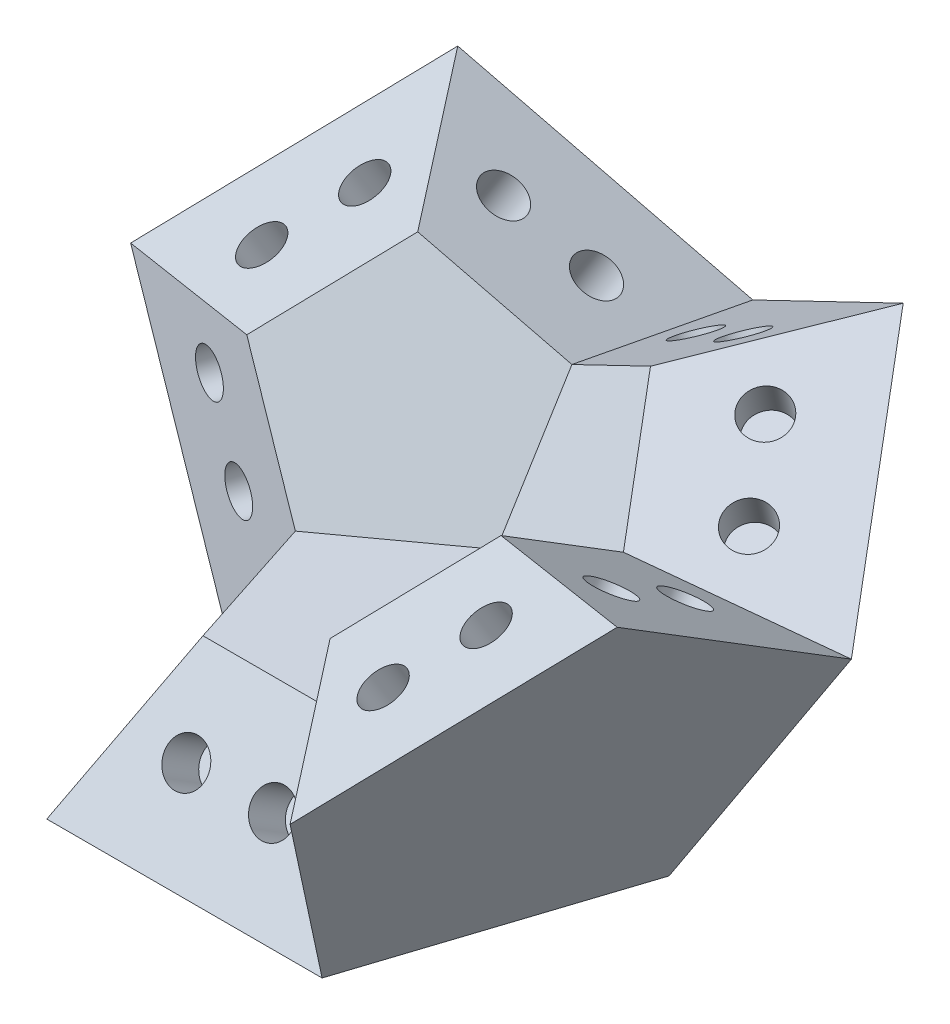
SolidWorks part; units mm, degrees
ref_plane "Front Plane" through (0, 0, 0) normal (0, 0, 1) x (1, 0, 0)
ref_plane "Top Plane" through (0, 0, 0) normal (0, 1, 0) x (1, 0, 0)
ref_plane "Right Plane" through (0, 0, 0) normal (1, 0, 0) x (0, 0, -1)
ref_axis "Axis1" through (0, 14.8487, 0) along (0, -1, 0)
sketch "Sketch1" plane through (0, 0, 0) normal (0, 1, 0) x (1, 0, 0)
  line L1 (0, 10.8033) -> (-10.2745, 3.3384)
  line L2 (-10.2745, 3.3384) -> (-6.35, -8.74)
  line L3 (-6.35, -8.74) -> (6.35, -8.74)
  line L4 (6.35, -8.74) -> (10.2745, 3.3384)
  line L5 (10.2745, 3.3384) -> (0, 10.8033)
  circle A0 centre (0, 0) radius 8.74 construction
  dimension "D1" = 12.7
extrude "Boss-Extrude1" add sketch "Sketch1" along normal blind 6.752 draft 31.717
mirror "Mirror1" [suppressed]
sketch "Sketch3" plane through (0, 3.9087, 6.3243) normal (0, 0.5257, 0.8507) x (1, 0, 0)
  line L0 (-2, -0.6262) -> (2, -0.6262) construction
  line L1 (-6.35, -4.5949) -> (6.35, -4.5949) construction
  line L2 (-2, -4.5949) -> (-2, 3.3426) construction
  circle A0 centre (-2, -0.6262) radius 1
  circle A1 centre (2, -0.6262) radius 1
  point P4 (0, -0.6262)
  point P5 (-2, -0.6262)
  dimension "D1" = 2
  dimension "D2" = 4
  dimension "D3" = 3.9688
extrude "Cut-Extrude1" cut sketch "Sketch3" against normal blind 2
pattern_circular "CirPattern1" count 5 over 360 about axis through (0, 14.8487, 0) along (0, -1, 0) of "Cut-Extrude1"
ref_plane "Plane1" through (-2, 6.752, 4.567) normal (0, -1, 0) x (-1, 0, 0)
mirror "Mirror3" about plane through (10.2745, 0, -3.3384) normal (0.5, 0.5257, -0.6882) of "Boss-Extrude1", "CirPattern1", "Cut-Extrude1"
mirror "Mirror4" about plane through (6.35, 0, 8.74) normal (0.809, 0.5257, 0.2629) of "CirPattern1", "Cut-Extrude1", "Boss-Extrude1"
mirror "Mirror5" about plane through (0, 0, -10.8033) normal (-0.5, 0.5257, -0.6882) of "CirPattern1", "Cut-Extrude1", "Boss-Extrude1"
equation "\"angle\"= arccos ( - sqr ( 5 ) / 5 )"
equation "\"theta\"= 90 - \"angle\" / 2"
equation "\"side\"=0.5"
equation "\"D1@Sketch1\"=\"side\""
equation "\"D3@Boss-Extrude1\"=\"theta\""
equation "\"D1@Boss-Extrude1\"=\"height\""
equation "\"face_height\"= .3125in"
equation "\"height\"= \"face_height\" * cos ( \"theta\" )"
